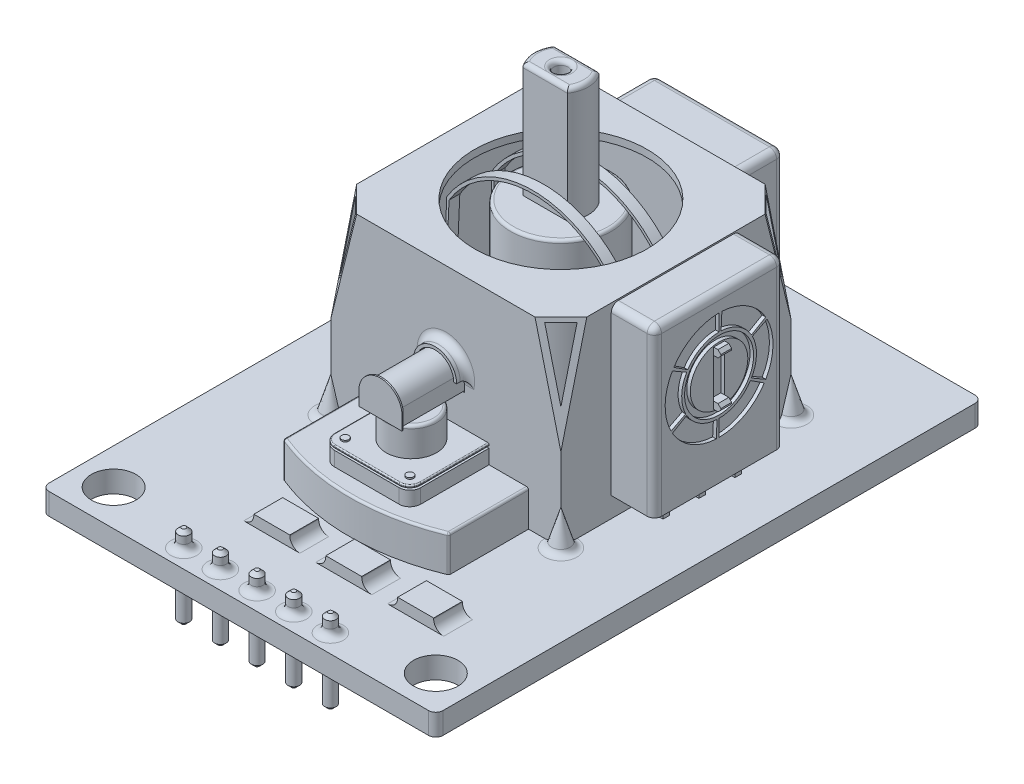
SolidWorks part; units mm, degrees
ref_plane "Front Plane" through (0, 0, 0) normal (0, 0, 1) x (1, 0, 0)
ref_plane "Top Plane" through (0, 0, 0) normal (0, 1, 0) x (1, 0, 0)
ref_plane "Right Plane" through (0, 0, 0) normal (1, 0, 0) x (0, 0, -1)
sketch "Sketch1" plane through (0, 0, 0) normal (0, 1, 0) x (1, 0, 0)
  line L1 (-13.2, -19) -> (13.2, -19)
  line L2 (-13.7, -18.5) -> (-13.7, 18.5)
  line L3 (-13.2, 19) -> (13.2, 19)
  line L4 (13.7, -18.5) -> (13.7, 18.5)
  line L5 (-13.7, -19) -> (13.7, 19) construction
  line L6 (-13.7, 19) -> (13.7, -19) construction
  circle A0 centre (-11.2, -16.5) radius 1.55
  circle A1 centre (11.2, -16.5) radius 1.55
  arc A2 (-13.7, 18.5) -> (-13.2, 19) centre (-13.2, 18.5) cw
  arc A3 (13.2, 19) -> (13.7, 18.5) centre (13.2, 18.5) cw
  arc A4 (13.2, -19) -> (13.7, -18.5) centre (13.2, -18.5) ccw
  arc A5 (-13.2, -19) -> (-13.7, -18.5) centre (-13.2, -18.5) cw
  point P0 (0, 0)
  point P12 (6.4069, -15.9996)
  dimension "D3" = 3.1
  dimension "D4" = 3.1
  dimension "D9" = 0.5
  dimension "D1" = 38
  dimension "D2" = 27.4
  dimension "D5" = 2.5
  dimension "D6" = 2.5
  dimension "D7" = 2.5
  dimension "D8" = 2.5
extrude "Boss-Extrude1" add sketch "Sketch1" along normal blind 1.5
sketch "Sketch2" plane through (0, 1.5, 0) normal (0, 1, 0) x (1, 0, 0)
  line L0 (13.2, 19) -> (-13.2, 19) construction
  line L1 (-8, -4.6) -> (8, -4.6)
  line L2 (-8, -4.6) -> (-8, 11.4)
  line L3 (-8, 11.4) -> (8, 11.4)
  line L4 (8, -4.6) -> (8, 11.4)
  line L5 (-8, -4.6) -> (8, 11.4) construction
  line L6 (-8, 11.4) -> (8, -4.6) construction
  point P0 (0, 3.4)
  point P8 (0, 0)
  dimension "D1" = 7.6
  dimension "D2" = 16
  dimension "D3" = 16
extrude "Boss-Extrude2" add sketch "Sketch2" along normal blind 13
sketch "Sketch3" plane through (0, 14.5, 0) normal (0, 1, 0) x (1, 0, 0)
  line L0 (-8, 11.4) -> (-8, -4.6) construction
  line L1 (8, 11.4) -> (-8, 11.4) construction
  circle A0 centre (0, 3.4) radius 6
  point P4 (-8, 3.4)
  point P5 (0, 0)
  point P8 (0, 11.4)
  dimension "D1" = 12
extrude "Cut-Extrude1" cut sketch "Sketch3" against normal blind 0.5
shell "Shell1" thickness 0.3 removed face at (0, 14, 2.6)
sketch "Sketch4" plane through (0, 14.5, 0) normal (0, 1, 0) x (1, 0, 0)
  line L0 (-6.2, -4.6) -> (-8, -2.8)
  line L1 (-8, -4.6) -> (8, -4.6) construction
  line L2 (-8, 11.4) -> (-8, -4.6) construction
  line L3 (-8, 9.6) -> (-6.2, 11.4)
  line L4 (8, 11.4) -> (-8, 11.4) construction
  line L5 (6.2, 11.4) -> (8, 9.6)
  line L6 (8, 11.4) -> (-8, 11.4) construction
  line L7 (8, -4.6) -> (8, 11.4) construction
  line L8 (8, -2.8) -> (6.2, -4.6)
  line L9 (-8, 9.6) -> (-8, -2.8)
  line L10 (-6.2, -4.6) -> (6.2, -4.6)
  line L11 (8, -2.8) -> (8, 9.6)
  line L12 (-6.2, 11.4) -> (6.2, 11.4)
  line L13 (-10.3421, 21.4) -> (10.3421, 21.4)
  line L14 (10.3421, 21.4) -> (18, 13.7421)
  line L15 (18, -6.9421) -> (18, 13.7421)
  line L16 (18, -6.9421) -> (10.3421, -14.6)
  line L17 (-10.3421, -14.6) -> (10.3421, -14.6)
  line L18 (-10.3421, -14.6) -> (-18, -6.9421)
  line L19 (-18, 13.7421) -> (-18, -6.9421)
  line L20 (-18, 13.7421) -> (-10.3421, 21.4)
  dimension "D1" = 1.8
  dimension "D2" = 1.8
  dimension "D3" = 1.8
  dimension "D4" = 1.8
  dimension "D5" = 1.8
  dimension "D6" = 1.8
  dimension "D7" = 1.8
  dimension "D8" = 1.8
  dimension "D9" = 10
extrude "Cut-Extrude2" cut sketch "Sketch4" against normal blind 10 draft 10
sketch "Sketch5" plane through (0, 1.5, 0) normal (0, 1, 0) x (1, 0, 0)
  circle A0 centre (-8, 11.4) radius 0.75
  circle A1 centre (-8, -4.6) radius 0.75
  circle A2 centre (8, -4.6) radius 0.75
  circle A3 centre (8, 11.4) radius 0.75
  dimension "D1" = 1.5
  dimension "D2" = 1.5
  dimension "D3" = 1.5
  dimension "D4" = 1.5
extrude "Boss-Extrude3" add sketch "Sketch5" along normal blind 5 draft 17
fillet "Fillet1" radius 0.5 4 edges at (8.5303, 1.5, -11.9303) (8.5303, 1.5, 5.1303) (-8.5303, 1.5, -11.9303) (-8.5303, 1.5, 5.1303)
sketch "Sketch6" plane through (0, 14.5, 0) normal (0, 1, 0) x (1, 0, 0)
  line L0 (-7.1, -3.7) -> (7.1, 10.5) construction
  line L1 (-8, -2.8) -> (-6.2, -4.6) construction
  line L2 (8, 9.6) -> (6.2, 11.4) construction
ref_plane "POT MIRROR" through (-1.7, 0, -1.7) normal (0.7071, 0, 0.7071) x (0.7071, 0, -0.7071)
sketch "Sketch7" plane through (0, 1.5, 0) normal (0, 1, 0) x (1, 0, 0)
  line L0 (8, -2.8) -> (8, 9.6) construction
  line L1 (8, -1.1) -> (10.5, -1.1)
  line L2 (8, -1.1) -> (8, 7.9)
  line L3 (8, 7.9) -> (10.5, 7.9)
  line L4 (11, -0.6) -> (11, 7.4)
  line L5 (-8, 10.28) -> (-8, -3.48) construction
  arc A0 (10.5, -1.1) -> (11, -0.6) centre (10.5, -0.6) ccw
  arc A1 (10.5, 7.9) -> (11, 7.4) centre (10.5, 7.4) cw
  point P6 (11, 3.4)
  point P9 (-8, 3.4)
  point P12 (11, -1.1)
  point P15 (11, 7.9)
  dimension "D3" = 0.5
  dimension "D1" = 3
  dimension "D2" = 9
extrude "Boss-Extrude4" add sketch "Sketch7" along normal blind 11.5 from offset 1.4
sketch "Sketch8" plane through (0, 1.5, 0) normal (0, 1, 0) x (1, 0, 0)
  line L0 (9.6, 0.9) -> (9.6, 5.9) construction
  line L1 (11, -0.6) -> (11, 7.4) construction
  line L3 (9.3764, 3.1764) -> (9.8236, 3.1764)
  line L4 (9.3764, 3.1764) -> (9.3764, 3.6236)
  line L5 (9.3764, 3.6236) -> (9.8236, 3.6236)
  line L6 (9.8236, 3.1764) -> (9.8236, 3.6236)
  line L7 (9.3764, 3.1764) -> (9.8236, 3.6236) construction
  line L8 (9.3764, 3.6236) -> (9.8236, 3.1764) construction
  line L9 (9.3764, 5.6764) -> (9.8236, 5.6764)
  line L10 (9.3764, 5.6764) -> (9.3764, 6.1236)
  line L11 (9.3764, 6.1236) -> (9.8236, 6.1236)
  line L12 (9.8236, 5.6764) -> (9.8236, 6.1236)
  line L13 (9.3764, 5.6764) -> (9.8236, 6.1236) construction
  line L14 (9.3764, 6.1236) -> (9.8236, 5.6764) construction
  line L15 (9.3764, 0.6764) -> (9.8236, 0.6764)
  line L16 (9.3764, 0.6764) -> (9.3764, 1.1236)
  line L17 (9.3764, 1.1236) -> (9.8236, 1.1236)
  line L18 (9.8236, 0.6764) -> (9.8236, 1.1236)
  line L19 (9.3764, 0.6764) -> (9.8236, 1.1236) construction
  line L20 (9.3764, 1.1236) -> (9.8236, 0.6764) construction
  point P0 (9.6, 3.4)
  point P3 (9.6, 3.4)
  point P6 (11, 3.4)
  point P19 (0, 0)
  point P20 (9.2052, 0.5052)
  point P21 (9.3764, 0.6764)
  dimension "D1" = 5
  dimension "D2" = 1.4
extrude "Boss-Extrude5" add sketch "Sketch8" along normal blind 5
sketch "Sketch9" plane through (11, 0, 0) normal (1, 0, 0) x (0, 0, -1)
  line L0 (7.9, 14.4) -> (-1.1, 14.4) construction
  line L1 (-0.6, 14.4) -> (7.4, 14.4) construction
  line L2 (3.4, 12) -> (3.4, 13.15)
  line L3 (3.5361, 11.9964) -> (3.5963, 13.1449)
  line L4 (5.7166, 10.5804) -> (6.7413, 11.1025)
  line L5 (5.6517, 10.7) -> (6.6476, 11.275)
  line L6 (5.5805, 7.9839) -> (6.545, 7.3576)
  line L7 (5.6517, 8.1) -> (6.6476, 7.525)
  line L8 (3.2639, 6.8036) -> (3.2037, 5.6551)
  line L9 (3.4, 6.8) -> (3.4, 5.65)
  line L10 (1.0834, 8.2196) -> (0.0587, 7.6975)
  line L11 (1.1483, 8.1) -> (0.1524, 7.525)
  line L12 (1.2195, 10.8161) -> (0.255, 11.4424)
  line L13 (1.1483, 10.7) -> (0.1524, 11.275)
  circle A0 centre (3.4, 9.4) radius 2
  circle A1 centre (3.4, 9.4) radius 2.4
  circle A2 centre (3.4, 9.4) radius 2.6
  circle A3 centre (3.4, 9.4) radius 3.75
  point P8 (3.4, 14.4)
  point P36 (3.4, 9.4)
  dimension "D2" = 4
  dimension "D3" = 4.8
  dimension "D4" = 5.2
  dimension "D5" = 7.5
  dimension "D1" = 5
  dimension "D6" = 3
  dimension "D7" = 6
extrude "Cut-Extrude3" cut sketch "Sketch9" against normal blind 0.25 contours A1 A0 | L13 A3 L10 A2 | L2 A3 L12 A2 | L5 A3 L3 A2 | L7 A3 L4 A2 | L9 A3 L6 A2 | L11 A3 L8 A2 region at (11, 12.1059, -1.9308) region at (11, 12.0253, -5.0088) region at (11, 9.4806, -0.3221) region at (11, 9.3194, -6.4779) region at (11, 6.7747, -1.7912) region at (11, 6.6941, -4.8692) region at (11, 9.4, -1.0679)
sketch "Sketch10" plane through (11, 0, 0) normal (1, 0, 0) x (0, 0, -1)
  line L1 (3.025, 8.025) -> (3.775, 8.025)
  line L2 (3.025, 8.025) -> (3.025, 10.775)
  line L3 (3.025, 10.775) -> (3.775, 10.775)
  line L4 (3.775, 8.025) -> (3.775, 10.775)
  line L5 (3.025, 8.025) -> (3.775, 10.775) construction
  line L6 (3.025, 10.775) -> (3.775, 8.025) construction
  point P0 (3.4, 9.4)
  dimension "D1" = 2.75
  dimension "D2" = 0.75
extrude "Cut-Extrude4" cut sketch "Sketch10" against normal blind 0.25
sketch "Sketch12" plane through (11, 0, 0) normal (1, 0, 0) x (0, 0, -1)
  line L0 (3.775, 8.025) -> (3.775, 10.775) construction
  line L1 (3.025, 10.775) -> (3.775, 10.775)
  line L2 (3.025, 10.775) -> (3.025, 11.275)
  line L3 (3.025, 11.275) -> (3.775, 11.275)
  line L4 (3.775, 10.775) -> (3.775, 11.275)
  line L5 (3.025, 9.4) -> (3.3288, 9.4) construction
  line L6 (3.025, 10.775) -> (3.025, 8.025) construction
  line L7 (3.025, 7.525) -> (3.775, 7.525)
  line L8 (3.775, 8.025) -> (3.775, 7.525)
  line L9 (3.025, 8.025) -> (3.775, 8.025)
  line L10 (3.025, 8.025) -> (3.025, 7.525)
  dimension "D1" = 0.5
extrude "Boss-Extrude6" add sketch "Sketch12" along normal blind 0.5
chamfer "Chamfer1" distance 0.2 angle 45 4 edges at (11.5, 7.525, -3.4) (11.5, 8.025, -3.4) (11.5, 10.775, -3.4) (11.5, 11.275, -3.4)
mirror "Mirror1" about plane through (-1.7, 0, -1.7) normal (0.7071, 0, 0.7071) of "Chamfer1", "Boss-Extrude6", "Cut-Extrude4", "Cut-Extrude3", "Boss-Extrude5", "Boss-Extrude4"
fillet "Fillet3" radius 0.5 10 edges at (-4.5, 14.4, -12.65) (-4.3536, 14.4, -14.2536) (4.5, 14.4, -12.65) (4.3536, 14.4, -14.2536) (9.25, 14.4, 1.1) (10.8536, 14.4, 0.9536) (9.25, 14.4, -7.9) (10.8536, 14.4, -7.7536) (0, 14.4, -14.4) (11, 14.4, -3.4)
sketch "Sketch13" plane through (0, 1.5, 0) normal (0, 1, 0) x (1, 0, 0)
  line L0 (-8, 10.28) -> (-8, -3.48) construction
  line L1 (-8, -0.6) -> (-9.5, -0.6)
  line L2 (-8, -0.6) -> (-8, 7.4)
  line L3 (-8, 7.4) -> (-9.5, 7.4)
  line L4 (-9.5, -0.6) -> (-9.5, 7.4)
  line L5 (8, -2.8) -> (8, 9.6) construction
  point P6 (-9.5, 3.4)
  point P9 (8, 3.4)
  dimension "D1" = 1.5
  dimension "D2" = 8
extrude "Boss-Extrude7" add sketch "Sketch13" along normal blind 5
chamfer "Chamfer2" distance 0.6 angle 45 3 edges at (-8.75, 6.5, -7.4) (-9.5, 6.5, -3.4) (-8.75, 6.5, 0.6)
sketch "Sketch14" plane through (0, 1.5, 0) normal (0, 1, 0) x (1, 0, 0)
  line L0 (-5.75, -4.6) -> (-5.75, -10.1288)
  line L1 (-6.2, -4.6) -> (6.2, -4.6) construction
  line L2 (5.75, -4.6) -> (5.75, -10.1288)
  line L3 (-5.75, -4.6) -> (5.75, -4.6)
  arc A0 (-5.75, -10.1288) -> (5.75, -10.1288) centre (0, 3.7254) ccw
  dimension "D3" = 15
  dimension "D1" = 11.5
  dimension "D2" = 5.75
extrude "Boss-Extrude8" add sketch "Sketch14" along normal blind 2.5
fillet "Fillet4" radius 0.15 5 edges at (5.75, 2.75, 10.1288) (-5.75, 2.75, 10.1288) (5.75, 4, 7.3644) (0, 4, 11.2746) (-5.75, 4, 7.3644)
sketch "Sketch15" plane through (0, 4, 0) normal (0, 1, 0) x (1, 0, 0)
  line L0 (5.6, -4.6) -> (-5.6, -4.6) construction
  line L1 (-3, -4.6) -> (3, -4.6)
  line L2 (-3, -4.6) -> (-3, -9.35)
  line L3 (-2.25, -10.1) -> (2.25, -10.1)
  line L4 (3, -4.6) -> (3, -9.35)
  arc A0 (2.25, -10.1) -> (3, -9.35) centre (2.25, -9.35) ccw
  arc A1 (-3, -9.35) -> (-2.25, -10.1) centre (-2.25, -9.35) ccw
  point P6 (0, -10.1)
  point P10 (3, -10.1)
  point P13 (-3, -10.1)
  dimension "D3" = 0.75
  dimension "D1" = 6
  dimension "D2" = 5.5
extrude "Boss-Extrude9" add sketch "Sketch15" along normal blind 1
sketch "Sketch17" plane through (0, 5, 0) normal (0, 1, 0) x (1, 0, 0)
  line L4 (-3, -4.6) -> (-3, -9.35)
  line L5 (-2.25, -10.1) -> (2.25, -10.1)
  line L6 (3, -9.35) -> (3, -4.6)
  line L7 (3, -4.6) -> (-3, -4.6)
  line L8 (-3, -4.6) -> (-3, -9.35)
  line L9 (-2.25, -10.1) -> (2.25, -10.1)
  line L10 (3, -9.35) -> (3, -4.6)
  line L11 (3, -4.6) -> (-3, -4.6)
  arc A2 (-3, -9.35) -> (-2.25, -10.1) centre (-2.25, -9.35) ccw
  arc A3 (2.25, -10.1) -> (3, -9.35) centre (2.25, -9.35) ccw
  arc A4 (-3, -9.35) -> (-2.25, -10.1) centre (-2.25, -9.35) ccw
  arc A5 (2.25, -10.1) -> (3, -9.35) centre (2.25, -9.35) ccw
  dimension "D1" = 0
extrude "Boss-Extrude10" add sketch "Sketch17" along normal blind 0.2 from offset 0.1
fillet "Fillet5" radius 0.08 10 edges at (-3, 5.3, 6.975) (3, 5.3, 6.975) (2.7803, 5.3, 9.8803) (0, 5.3, 10.1) (-3, 5.1, 6.975) (3, 5.1, 6.975) (2.7803, 5.1, 9.8803) (0, 5.1, 10.1) (-2.7803, 5.3, 9.8803) (-2.7803, 5.1, 9.8803)
sketch "Sketch18" plane through (0, 5.3, 0) normal (0, 1, 0) x (1, 0, 0)
  circle A0 centre (-2.25, -9.35) radius 0.25
  circle A1 centre (2.25, -9.35) radius 0.25
  dimension "D1" = 0.5
  dimension "D2" = 0.5
extrude "Boss-Extrude11" add sketch "Sketch18" along normal blind 0.1
sketch "Sketch19" plane through (0, 0, 4.6) normal (0, 0, 1) x (1, 0, 0)
  line L0 (-6.2, 14.5) -> (6.2, 14.5) construction
  line L1 (-1.5, 8.5) -> (1.5, 8.5)
  arc A0 (1.5, 8.5) -> (-1.5, 8.5) centre (0, 8.5) ccw
  dimension "D2" = 1.5
  dimension "D1" = 6
extrude "Boss-Extrude12" add sketch "Sketch19" along normal blind 0.75
fillet "Fillet6" radius 0.5 2 edges at (0, 10, 4.6) (0, 8.5, 4.6)
sketch "Sketch20" plane through (0, 0, 5.35) normal (0, 0, 1) x (1, 0, 0)
  line L2 (-1.2845, 8.7) -> (1.2845, 8.7)
  line L3 (-1.2845, 8.7) -> (1.2845, 8.7)
  line L4 (-1.2845, 8.7) -> (1.2845, 8.7)
  line L5 (-1.2845, 8.7) -> (-1.2845, 7.5)
  line L6 (-1.2845, 7.5) -> (1.2845, 7.5)
  line L7 (1.2845, 8.7) -> (1.2845, 7.5)
  arc A2 (1.2845, 8.7) -> (-1.2845, 8.7) centre (0, 8.5) ccw
  arc A3 (1.2845, 8.7) -> (-1.2845, 8.7) centre (0, 8.5) ccw
  line M8 (-1.5, 8.5) -> (1.5, 8.5)
  dimension "D2" = 1.2
  dimension "D1" = 0.2
extrude "Cut-Extrude5" cut sketch "Sketch20" against normal blind 2.75 contours L7 L5 L6 M8 | L3 A3 | L7 L3 L5 M8 region at (0, 9.1613, 5.35) region at (0, 8.6, 5.35) region at (0, 8, 5.35)
sketch "Sketch21" plane through (0, 0, 4.3) normal (0, 0, -1) x (-1, 0, 0)
  line L0 (-1.2845, 8.7) -> (-1.2845, 8.5) construction
  line L1 (-1.2845, 8) -> (-1.2845, 8.5) construction
  line L2 (-1.2845, 7.5) -> (-1.2845, 8) construction
  line L5 (-1.2845, 7.5) -> (1.2845, 7.5) construction
  line L6 (1.2845, 7.5) -> (1.2845, 8) construction
  line L7 (1.2845, 8.5) -> (1.2845, 8) construction
  line L8 (1.2845, 8.7) -> (1.2845, 8.5) construction
  line L9 (-1.2845, 8.7) -> (-1.2845, 8.5) construction
  line L10 (-1.2845, 8) -> (-1.2845, 8.5) construction
  line L11 (-1.2845, 7.5) -> (-1.2845, 8) construction
  line L12 (-1.2845, 7.5) -> (1.2845, 7.5) construction
  line L13 (1.2845, 7.5) -> (1.2845, 8) construction
  line L14 (1.2845, 8.5) -> (1.2845, 8) construction
  line L15 (1.2845, 8.7) -> (1.2845, 8.5) construction
  line L16 (-1.2345, 8.6961) -> (-1.2345, 8.5)
  line L17 (-1.2345, 8) -> (-1.2345, 8.5)
  line L18 (-1.2345, 7.55) -> (-1.2345, 8)
  line L19 (-1.2345, 7.55) -> (1.2345, 7.55)
  line L20 (1.2345, 7.55) -> (1.2345, 8)
  line L21 (1.2345, 8.5) -> (1.2345, 8)
  line L22 (1.2345, 8.6961) -> (1.2345, 8.5)
  arc A0 (1.2845, 8.7) -> (-1.2845, 8.7) centre (0, 8.5) ccw construction
  arc A1 (1.2845, 8.7) -> (-1.2845, 8.7) centre (0, 8.5) ccw construction
  arc A2 (1.2345, 8.6961) -> (-1.2345, 8.6961) centre (0, 8.5) ccw
  dimension "D1" = 0.05
extrude "Boss-Extrude13" add sketch "Sketch21" against normal blind 4.75 separate body
sketch "Sketch22" plane through (0, 0, 9.05) normal (0, 0, 1) x (1, 0, 0)
  line L6 (-1.4845, 8.7149) -> (-1.4845, 7.3)
  line L7 (-1.4845, 7.3) -> (1.4845, 7.3)
  line L8 (1.4845, 7.3) -> (1.4845, 8.7149)
  line L9 (-1.4845, 8.7149) -> (-1.4845, 7.3)
  line L10 (-1.4845, 7.3) -> (1.4845, 7.3)
  line L11 (1.4845, 7.3) -> (1.4845, 8.7149)
  arc A2 (1.4845, 8.7149) -> (-1.4845, 8.7149) centre (0, 8.5) ccw
  arc A3 (1.4845, 8.7149) -> (-1.4845, 8.7149) centre (0, 8.5) ccw
  dimension "D1" = 0.25
extrude "Boss-Extrude14" add sketch "Sketch22" along normal blind 0.1
sketch "Sketch23" plane through (-1.2345, 0, 0) normal (-1, 0, 0) x (0, 0, 1)
  line L0 (9.05, 7.55) -> (9.15, 7.55)
  line L1 (9.15, 8.7149) -> (9.15, 7.3) construction
  line L2 (9.15, 7.55) -> (9.15, 7.3)
  line L3 (9.15, 7.3) -> (9.05, 7.3)
  line L4 (9.05, 7.3) -> (9.05, 7.55)
extrude "Cut-Extrude6" cut sketch "Sketch23" against normal through all and the other way through all
sketch "Sketch24" plane through (0, 5.3, 0) normal (0, 1, 0) x (1, 0, 0)
  circle A0 centre (0, -7) radius 1.75
  point P2 (0, -6.9174)
  dimension "D1" = 3.5
  dimension "D2" = 7
extrude "Boss-Extrude15" add sketch "Sketch24" along normal blind 2
fillet "Fillet7" radius 0.2 1 edges at (0, 7.3, 8.75)
sketch "Sketch25" plane through (0, 0.3, 0) normal (0, 1, 0) x (1, 0, 0)
  circle A0 centre (0, 3.4) radius 3.5
  dimension "D1" = 7
extrude "Boss-Extrude16" add sketch "Sketch25" along normal up to surface (14.2 mm away) up to face at (0, 14.5, 2.6)
fillet "Fillet8" radius 0.2 1 edges at (0, 14.5, -6.9)
sketch "Sketch26" plane through (0, 14.5, 0) normal (0, 1, 0) x (1, 0, 0)
  line L0 (-1.5492, 4.5) -> (1.5492, 4.5)
  line L1 (-1.5492, 2.3) -> (1.5492, 2.3)
  circle A0 centre (0, 3.4) radius 1.9
  circle A1 centre (0, 3.4) radius 0.5
  dimension "D1" = 3.8
  dimension "D3" = 1
  dimension "D2" = 1.1
extrude "Boss-Extrude17" add sketch "Sketch26" along normal blind 8 contours L1 A0 L0 A1 region at (0, 14.5, -4.4561)
fillet "Fillet9" radius 0.3 5 edges at (-1.9, 22.5, -3.4) (0, 22.5, -4.5) (1.9, 22.5, -3.4) (0, 22.5, -2.3) (0, 22.5, -2.9)
sketch "Sketch27" plane through (0, 14.5, 0) normal (0, 1, 0) x (1, 0, 0)
  line L0 (-8, 3.4) -> (8, 3.4) construction
  line L1 (-8, 0) -> (-8, 6.8) construction
  line L2 (8, -2.8) -> (8, 9.6) construction
ref_plane "Carriage mirror" through (0, 0, -3.4) normal (0, 0, 1) x (1, 0, 0)
sketch "Sketch28" plane through (0, 0, -3.4) normal (0, 0, 1) x (1, 0, 0)
  line L3 (-5.8286, 12.5025) -> (-6.315, 1.5)
  line L4 (-6.88, 1.5) -> (-5.75, 1.5) construction
  line L5 (-6.315, 1.5) -> (-6, 12.6056)
  line L6 (6, 12.6056) -> (6.315, 1.5)
  line L7 (5.75, 1.5) -> (6.88, 1.5) construction
  line L8 (6.315, 1.5) -> (5.8286, 12.5025)
  arc A0 (-6, 12.6056) -> (6, 12.6056) centre (0, 9) cw
  arc A1 (-5.8286, 12.5025) -> (5.8286, 12.5025) centre (0, 9) cw
  point P3 (0, 15.8)
  dimension "D3" = 7
  dimension "D1" = 12
  dimension "D2" = 9
  dimension "D4" = 0.2
extrude "Boss-Extrude18" add sketch "Sketch28" along normal blind 0.75 from offset 1.2 separate body
sketch "Sketch29" plane through (0, 0, -3.4) normal (0, 0, 1) x (1, 0, 0)
  line L4 (-6.315, 1.5) -> (-5.8286, 12.5025)
  line L5 (-6, 12.6056) -> (-6.315, 1.5)
  line L6 (6.315, 1.5) -> (6, 12.6056)
  line L7 (5.8286, 12.5025) -> (6.315, 1.5)
  line L8 (-6.315, 1.5) -> (-5.8286, 12.5025)
  line L9 (-6, 12.6056) -> (-6.315, 1.5)
  line L10 (6.315, 1.5) -> (6, 12.6056)
  line L11 (5.8286, 12.5025) -> (6.315, 1.5)
  arc A2 (6, 12.6056) -> (-6, 12.6056) centre (0, 9) ccw
  arc A3 (5.8286, 12.5025) -> (-5.8286, 12.5025) centre (0, 9) ccw
  arc A4 (6, 12.6056) -> (-6, 12.6056) centre (0, 9) ccw
  arc A5 (5.8286, 12.5025) -> (-5.8286, 12.5025) centre (0, 9) ccw
  dimension "D1" = 0
extrude "Boss-Extrude19" add sketch "Sketch29" against normal blind 0.75 from offset 1.2 separate body offset against normal yes
sketch "Sketch30" plane through (0, 1.5, 0) normal (0, 1, 0) x (1, 0, 0)
  line L0 (-13.2, -19) -> (13.2, -19) construction
  line L1 (-3.95, -12) -> (-1.45, -12)
  line L2 (-3.95, -12) -> (-3.95, -14)
  line L3 (-3.95, -14) -> (-1.45, -14)
  line L4 (-1.45, -12) -> (-1.45, -14)
  line L5 (-3.95, -12) -> (-1.45, -14) construction
  line L6 (-3.95, -14) -> (-1.45, -12) construction
  line L7 (-13.7, 18.5) -> (-13.7, -18.5) construction
  point P0 (-2.7, -13)
  dimension "D1" = 2.5
  dimension "D2" = 2
  dimension "D3" = 6
  dimension "D4" = 11
extrude "Boss-Extrude20" add sketch "Sketch30" along normal blind 0.75
fillet "Fillet10" radius 0.7 2 edges at (-1.45, 1.5, 13) (-3.95, 1.5, 13)
pattern_linear "LPattern1" count 3 spacing 5 along (1, 0, 0) of "Boss-Extrude20", "Fillet10"
sketch "Sketch31" plane through (0, 1.5, 0) normal (0, 1, 0) x (1, 0, 0)
  line L0 (-13.2, -19) -> (13.2, -19) construction
  circle A0 centre (0, -17.725) radius 0.4
  point P4 (0, 0)
  dimension "D1" = 0.8
  dimension "D2" = 1.275
extrude "Boss-Extrude21" add sketch "Sketch31" along normal blind 1.25
pattern_linear "LPattern2" count 3 spacing 2.55 along (-1, 0, 0) count 3 spacing 2.55 along (1, 0, 0) of "Boss-Extrude21"
fillet "Fillet11" radius 0.5 5 edges at (5.1, 1.5, 17.325) (2.55, 1.5, 17.325) (0, 1.5, 17.325) (-2.55, 1.5, 17.325) (-5.1, 1.5, 17.325)
chamfer "Chamfer3" distance 0.25 angle 45 5 edges at (5.1, 2.75, 18.125) (2.55, 2.75, 18.125) (0, 2.75, 18.125) (-2.55, 2.75, 18.125) (-5.1, 2.75, 18.125)
sketch "Sketch32" plane through (0, 0, 0) normal (0, -1, 0) x (1, 0, 0)
  circle A1 centre (0, 17.725) radius 0.4
  circle A2 centre (0, 17.725) radius 0.4
  dimension "D1" = 0
extrude "Boss-Extrude22" add sketch "Sketch32" along normal blind 3
pattern_linear "LPattern5" count 3 spacing 2.55 along (1, 0, 0) count 3 spacing 2.55 along (-1, 0, 0) of "Boss-Extrude22"
chamfer "Chamfer4" distance 0.25 angle 45 5 edges at (0, -3, 17.325) (-5.1, -3, 17.325) (-2.55, -3, 17.325) (5.1, -3, 17.325) (2.55, -3, 17.325)
